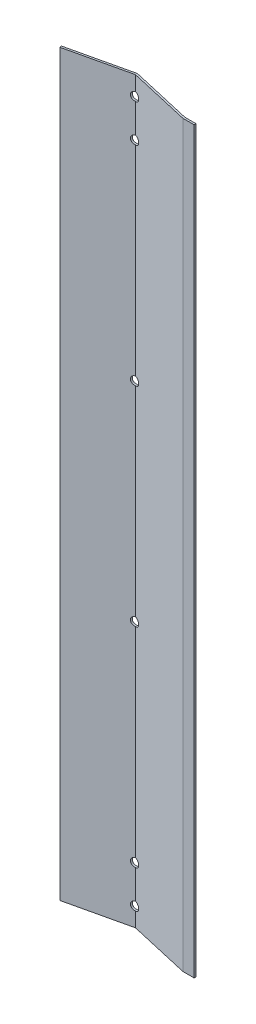
SolidWorks part; units mm, degrees
material "ASTM A36 Steel"
ref_plane "Front Plane" through (0, 0, 0) normal (0, 0, 1) x (1, 0, 0)
ref_plane "Top Plane" through (0, 0, 0) normal (0, 1, 0) x (1, 0, 0)
ref_plane "Right Plane" through (0, 0, 0) normal (1, 0, 0) x (0, 0, -1)
sketch "Sketch1" plane through (0, 0, 0) normal (0, 1, 0) x (1, 0, 0)
  line L0 (-506.6276, -999.7048) -> (-536.6276, -999.7048)
  line L1 (-536.6276, -999.7048) -> (-699.6276, -962.3438)
  line L2 (-699.6276, -962.3438) -> (-862.6276, -999.7048)
  line L3 (-862.6276, -999.7048) -> (-863.6948, -994.82)
  line L4 (-863.6948, -994.82) -> (-699.6276, -957.2258)
  line L5 (-699.6276, -957.2258) -> (-536.0877, -994.7048)
  line L6 (-536.0877, -994.7048) -> (-506.6276, -994.7048)
  line L7 (-506.6276, -994.7048) -> (-506.6276, -999.7048)
extrude "Boss-Extrude1" add sketch "Sketch1" along normal blind 1960
sketch "Sketch2" plane through (0, 0, 0) normal (0, 0, 1) x (1, 0, 0)
  line L0 (-699.6276, 1960) -> (-699.6276, 0) construction
  line L1 (-699.6276, 0) -> (-536.6276, 0) construction
  line L2 (-862.6276, 1960) -> (-699.6276, 1960) construction
  circle A0 centre (-699.6276, 50) radius 11
  circle A1 centre (-699.6276, 150) radius 11
  circle A2 centre (-699.6276, 1910) radius 11
  circle A3 centre (-699.6276, 1810) radius 11
  circle A4 centre (-699.6276, 703.33) radius 11
  circle A5 centre (-699.6276, 1256.66) radius 11
  dimension "D1" = 22
  dimension "D3" = 100
  dimension "D4" = 22
  dimension "D5" = 22
  dimension "D6" = 22
  dimension "D7" = 50
  dimension "D8" = 100
  dimension "D9" = 553.33
  dimension "D10" = 22
  dimension "D11" = 553.33
  dimension "D12" = 22
  dimension "D2" = 50
extrude "Cut-Extrude1" cut sketch "Sketch2" against normal through all both and the other way through all
